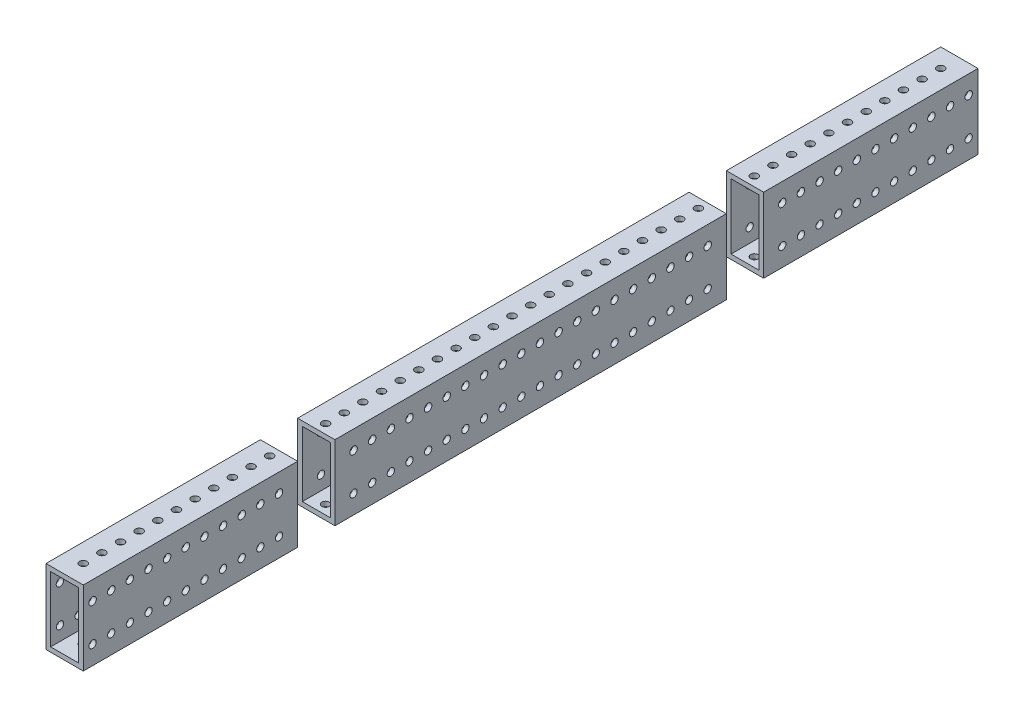
SolidWorks part; units mm, degrees
material "6061-T6 (SS)"
ref_plane "Front Plane" through (0, 0, 0) normal (0, 0, 1) x (1, 0, 0)
ref_plane "Top Plane" through (0, 0, 0) normal (0, 1, 0) x (1, 0, 0)
ref_plane "Right Plane" through (0, 0, 0) normal (1, 0, 0) x (0, 0, -1)
sketch "Sketch1" plane through (0, 0, 0) normal (0, 0, 1) x (1, 0, 0)
  line L0 (-9.525, 22.225) -> (9.525, 22.225)
  line L1 (-12.7, 25.4) -> (12.7, 25.4)
  line L2 (-12.7, 25.4) -> (-12.7, -25.4)
  line L3 (-12.7, -25.4) -> (12.7, -25.4)
  line L4 (12.7, 25.4) -> (12.7, -25.4)
  line L5 (9.525, 22.225) -> (9.525, -22.225)
  line L6 (-9.525, -22.225) -> (9.525, -22.225)
  line L7 (-9.525, 22.225) -> (-9.525, -22.225)
  line L8 (-12.7, 25.4) -> (12.7, -25.4) construction
  line L9 (12.7, 25.4) -> (-12.7, -25.4) construction
  point P5 (0, 0)
  dimension "D1" = 25.4
  dimension "D2" = 50.8
  dimension "D3" = 3.175
extrude "Boss-Extrude1" add sketch "Sketch1" along normal mid plane 609.6
sketch "Sketch2" plane through (0, 25.4, 0) normal (0, 1, 0) x (1, 0, 0)
  line L0 (12.7, -304.8) -> (-12.7, -304.8) construction
  line L1 (-12.7, -304.8) -> (-12.7, 304.8) construction
  line L4 (12.7, 304.8) -> (-12.7, 304.8) construction
  circle A0 centre (12.7, -292.1) radius 2.5527 construction
  circle A1 centre (25.4, -292.1) radius 2.5527 construction
  circle A2 centre (0, -292.1) radius 2.5527
  circle A3 centre (0, -279.4) radius 2.5527
  circle A4 centre (12.7, -279.4) radius 2.5527 construction
  circle A5 centre (25.4, -279.4) radius 2.5527 construction
  circle A6 centre (0, -266.7) radius 2.5527
  circle A7 centre (12.7, -266.7) radius 2.5527 construction
  circle A8 centre (25.4, -266.7) radius 2.5527 construction
  circle A9 centre (0, -254) radius 2.5527
  circle A10 centre (12.7, -254) radius 2.5527 construction
  circle A11 centre (25.4, -254) radius 2.5527 construction
  circle A12 centre (0, -241.3) radius 2.5527
  circle A13 centre (12.7, -241.3) radius 2.5527 construction
  circle A14 centre (25.4, -241.3) radius 2.5527 construction
  circle A15 centre (0, -228.6) radius 2.5527
  circle A16 centre (12.7, -228.6) radius 2.5527 construction
  circle A17 centre (25.4, -228.6) radius 2.5527 construction
  circle A18 centre (0, -215.9) radius 2.5527
  circle A19 centre (12.7, -215.9) radius 2.5527 construction
  circle A20 centre (25.4, -215.9) radius 2.5527 construction
  circle A21 centre (0, -203.2) radius 2.5527
  circle A22 centre (12.7, -203.2) radius 2.5527 construction
  circle A23 centre (25.4, -203.2) radius 2.5527 construction
  circle A24 centre (0, -190.5) radius 2.5527
  circle A25 centre (12.7, -190.5) radius 2.5527 construction
  circle A26 centre (25.4, -190.5) radius 2.5527 construction
  circle A27 centre (0, -177.8) radius 2.5527
  circle A28 centre (12.7, -177.8) radius 2.5527 construction
  circle A29 centre (25.4, -177.8) radius 2.5527 construction
  circle A30 centre (0, -165.1) radius 2.5527
  circle A31 centre (12.7, -165.1) radius 2.5527 construction
  circle A32 centre (25.4, -165.1) radius 2.5527 construction
  circle A33 centre (0, -152.4) radius 2.5527
  circle A34 centre (12.7, -152.4) radius 2.5527 construction
  circle A35 centre (25.4, -152.4) radius 2.5527 construction
  circle A36 centre (0, -139.7) radius 2.5527
  circle A37 centre (12.7, -139.7) radius 2.5527 construction
  circle A38 centre (25.4, -139.7) radius 2.5527 construction
  circle A39 centre (0, -127) radius 2.5527
  circle A40 centre (12.7, -127) radius 2.5527 construction
  circle A41 centre (25.4, -127) radius 2.5527 construction
  circle A42 centre (0, -114.3) radius 2.5527
  circle A43 centre (12.7, -114.3) radius 2.5527 construction
  circle A44 centre (25.4, -114.3) radius 2.5527 construction
  circle A45 centre (0, -101.6) radius 2.5527
  circle A46 centre (12.7, -101.6) radius 2.5527 construction
  circle A47 centre (25.4, -101.6) radius 2.5527 construction
  circle A48 centre (0, -88.9) radius 2.5527
  circle A49 centre (12.7, -88.9) radius 2.5527 construction
  circle A50 centre (25.4, -88.9) radius 2.5527 construction
  circle A51 centre (0, -76.2) radius 2.5527
  circle A52 centre (12.7, -76.2) radius 2.5527 construction
  circle A53 centre (25.4, -76.2) radius 2.5527 construction
  circle A54 centre (0, -63.5) radius 2.5527
  circle A55 centre (12.7, -63.5) radius 2.5527 construction
  circle A56 centre (25.4, -63.5) radius 2.5527 construction
  circle A57 centre (0, -50.8) radius 2.5527
  circle A58 centre (12.7, -50.8) radius 2.5527 construction
  circle A59 centre (25.4, -50.8) radius 2.5527 construction
  circle A60 centre (0, -38.1) radius 2.5527
  circle A61 centre (12.7, -38.1) radius 2.5527 construction
  circle A62 centre (25.4, -38.1) radius 2.5527 construction
  circle A63 centre (0, -25.4) radius 2.5527
  circle A64 centre (12.7, -25.4) radius 2.5527 construction
  circle A65 centre (25.4, -25.4) radius 2.5527 construction
  circle A66 centre (0, -12.7) radius 2.5527
  circle A67 centre (12.7, -12.7) radius 2.5527 construction
  circle A68 centre (25.4, -12.7) radius 2.5527 construction
  circle A69 centre (0, 0) radius 2.5527
  circle A70 centre (12.7, 0) radius 2.5527 construction
  circle A71 centre (25.4, 0) radius 2.5527 construction
  circle A72 centre (0, 12.7) radius 2.5527
  circle A73 centre (12.7, 12.7) radius 2.5527 construction
  circle A74 centre (25.4, 12.7) radius 2.5527 construction
  circle A75 centre (0, 25.4) radius 2.5527
  circle A76 centre (12.7, 25.4) radius 2.5527 construction
  circle A77 centre (25.4, 25.4) radius 2.5527 construction
  circle A78 centre (0, 38.1) radius 2.5527
  circle A79 centre (12.7, 38.1) radius 2.5527 construction
  circle A80 centre (25.4, 38.1) radius 2.5527 construction
  circle A81 centre (0, 50.8) radius 2.5527
  circle A82 centre (12.7, 50.8) radius 2.5527 construction
  circle A83 centre (25.4, 50.8) radius 2.5527 construction
  circle A84 centre (0, 63.5) radius 2.5527
  circle A85 centre (12.7, 63.5) radius 2.5527 construction
  circle A86 centre (25.4, 63.5) radius 2.5527 construction
  circle A87 centre (0, 76.2) radius 2.5527
  circle A88 centre (12.7, 76.2) radius 2.5527 construction
  circle A89 centre (25.4, 76.2) radius 2.5527 construction
  circle A90 centre (0, 88.9) radius 2.5527
  circle A91 centre (12.7, 88.9) radius 2.5527 construction
  circle A92 centre (25.4, 88.9) radius 2.5527 construction
  circle A93 centre (0, 101.6) radius 2.5527
  circle A94 centre (12.7, 101.6) radius 2.5527 construction
  circle A95 centre (25.4, 101.6) radius 2.5527 construction
  circle A96 centre (0, 114.3) radius 2.5527
  circle A97 centre (12.7, 114.3) radius 2.5527 construction
  circle A98 centre (25.4, 114.3) radius 2.5527 construction
  circle A99 centre (0, 127) radius 2.5527
  circle A100 centre (12.7, 127) radius 2.5527 construction
  circle A101 centre (25.4, 127) radius 2.5527 construction
  circle A108 centre (0, 152.4) radius 2.5527 [skipped]
  circle A109 centre (12.7, 152.4) radius 2.5527 [skipped]
  circle A110 centre (25.4, 152.4) radius 2.5527 [skipped]
  circle A111 centre (0, 139.7) radius 2.5527 [skipped]
  circle A112 centre (12.7, 139.7) radius 2.5527 [skipped]
  circle A113 centre (25.4, 139.7) radius 2.5527 [skipped]
  circle A114 centre (25.4, 139.7) radius 2.5527 construction
  circle A115 centre (12.7, 139.7) radius 2.5527 construction
  circle A116 centre (0, 139.7) radius 2.5527
  circle A117 centre (25.4, 152.4) radius 2.5527 construction
  circle A118 centre (12.7, 152.4) radius 2.5527 construction
  circle A119 centre (0, 152.4) radius 2.5527
  circle A120 centre (25.4, 165.1) radius 2.5527 construction
  circle A121 centre (12.7, 165.1) radius 2.5527 construction
  circle A122 centre (0, 165.1) radius 2.5527
  circle A123 centre (25.4, 177.8) radius 2.5527 construction
  circle A124 centre (12.7, 177.8) radius 2.5527 construction
  circle A125 centre (0, 177.8) radius 2.5527
  circle A126 centre (25.4, 190.5) radius 2.5527 construction
  circle A127 centre (12.7, 190.5) radius 2.5527 construction
  circle A128 centre (0, 190.5) radius 2.5527
  circle A129 centre (25.4, 203.2) radius 2.5527 construction
  circle A130 centre (12.7, 203.2) radius 2.5527 construction
  circle A131 centre (0, 203.2) radius 2.5527
  circle A132 centre (25.4, 215.9) radius 2.5527 construction
  circle A133 centre (12.7, 215.9) radius 2.5527 construction
  circle A134 centre (0, 215.9) radius 2.5527
  circle A135 centre (25.4, 228.6) radius 2.5527 construction
  circle A136 centre (12.7, 228.6) radius 2.5527 construction
  circle A137 centre (0, 228.6) radius 2.5527
  circle A138 centre (25.4, 241.3) radius 2.5527 construction
  circle A139 centre (12.7, 241.3) radius 2.5527 construction
  circle A140 centre (0, 241.3) radius 2.5527
  circle A141 centre (25.4, 254) radius 2.5527 construction
  circle A142 centre (12.7, 254) radius 2.5527 construction
  circle A143 centre (0, 254) radius 2.5527
  circle A144 centre (25.4, 266.7) radius 2.5527 construction
  circle A145 centre (12.7, 266.7) radius 2.5527 construction
  circle A146 centre (0, 266.7) radius 2.5527
  circle A147 centre (25.4, 279.4) radius 2.5527 construction
  circle A148 centre (12.7, 279.4) radius 2.5527 construction
  circle A149 centre (0, 279.4) radius 2.5527
  circle A150 centre (25.4, 292.1) radius 2.5527 construction
  circle A151 centre (12.7, 292.1) radius 2.5527 construction
  circle A152 centre (0, 292.1) radius 2.5527
  dimension "D2" = 5.1054
  dimension "D4" = 12.7
  dimension "D1" = 12.7
  dimension "D3" = 25.4
  dimension "D6" = 12.7
  dimension "D7" = 177.8
  dimension "D5" = 36
  dimension "D8" = 14
extrude "Cut-Extrude1" cut sketch "Sketch2" against normal through all
sketch "Sketch4" plane through (12.7, 0, 0) normal (1, 0, 0) x (0, 0, -1)
  line L0 (-304.8, 25.4) -> (304.8, 25.4) construction
  line L1 (-304.8, -25.4) -> (-304.8, 25.4) construction
  line L2 (-304.8, -25.4) -> (304.8, -25.4) construction
  line L3 (-304.8, 25.4) -> (-304.8, -25.4) construction
  circle A2 centre (-298.45, -12.7) radius 2.4892
  circle A3 centre (-285.75, -12.7) radius 2.4892
  circle A16 centre (-273.05, -12.7) radius 2.4892
  circle A17 centre (-260.35, -12.7) radius 2.4892
  circle A18 centre (-247.65, -12.7) radius 2.4892
  circle A19 centre (133.35, -12.7) radius 2.4892 construction
  circle A20 centre (146.05, -12.7) radius 2.4892
  circle A21 centre (158.75, -12.7) radius 2.4892 construction
  circle A22 centre (171.45, -12.7) radius 2.4892
  circle A23 centre (184.15, -12.7) radius 2.4892
  circle A24 centre (196.85, -12.7) radius 2.4892
  circle A25 centre (209.55, -12.7) radius 2.4892
  circle A26 centre (222.25, -12.7) radius 2.4892
  circle A27 centre (234.95, -12.7) radius 2.4892
  circle A28 centre (247.65, -12.7) radius 2.4892
  circle A29 centre (260.35, -12.7) radius 2.4892
  circle A30 centre (273.05, -12.7) radius 2.4892
  circle A31 centre (285.75, -12.7) radius 2.4892
  circle A32 centre (298.45, -12.7) radius 2.4892
  circle A33 centre (-298.45, 12.7) radius 2.5527
  circle A34 centre (-285.75, 12.7) radius 2.5527
  circle A35 centre (-234.95, -12.7) radius 2.4892
  circle A36 centre (-222.25, -12.7) radius 2.4892
  circle A37 centre (-209.55, -12.7) radius 2.4892
  circle A38 centre (-196.85, -12.7) radius 2.4892
  circle A39 centre (-184.15, -12.7) radius 2.4892
  circle A40 centre (-171.45, -12.7) radius 2.4892
  circle A41 centre (-158.75, -12.7) radius 2.4892 construction
  circle A42 centre (-146.05, -12.7) radius 2.4892
  circle A43 centre (-133.35, -12.7) radius 2.4892 construction
  circle A44 centre (-120.65, -12.7) radius 2.4892
  circle A45 centre (-107.95, -12.7) radius 2.4892
  circle A46 centre (-95.25, -12.7) radius 2.4892
  circle A47 centre (-82.55, -12.7) radius 2.4892
  circle A48 centre (-69.85, -12.7) radius 2.4892
  circle A49 centre (-57.15, -12.7) radius 2.4892
  circle A50 centre (-44.45, -12.7) radius 2.4892
  circle A51 centre (-31.75, -12.7) radius 2.4892
  circle A52 centre (-19.05, -12.7) radius 2.4892
  circle A53 centre (-6.35, -12.7) radius 2.4892
  circle A54 centre (6.35, -12.7) radius 2.4892
  circle A55 centre (19.05, -12.7) radius 2.4892
  circle A56 centre (31.75, -12.7) radius 2.4892
  circle A57 centre (44.45, -12.7) radius 2.4892
  circle A58 centre (57.15, -12.7) radius 2.4892
  circle A59 centre (69.85, -12.7) radius 2.4892
  circle A60 centre (82.55, -12.7) radius 2.4892
  circle A61 centre (95.25, -12.7) radius 2.4892
  circle A62 centre (107.95, -12.7) radius 2.4892
  circle A63 centre (120.65, -12.7) radius 2.4892
  circle A64 centre (-273.05, 12.7) radius 2.5527
  circle A65 centre (-260.35, 12.7) radius 2.5527
  circle A66 centre (-247.65, 12.7) radius 2.5527
  circle A67 centre (-234.95, 12.7) radius 2.5527
  circle A68 centre (-222.25, 12.7) radius 2.5527
  circle A69 centre (-209.55, 12.7) radius 2.5527
  circle A70 centre (-196.85, 12.7) radius 2.5527
  circle A71 centre (-184.15, 12.7) radius 2.5527
  circle A72 centre (-171.45, 12.7) radius 2.5527
  circle A73 centre (-158.75, 12.7) radius 2.5527 construction
  circle A74 centre (-146.05, 12.7) radius 2.5527
  circle A75 centre (-133.35, 12.7) radius 2.5527 construction
  circle A76 centre (-120.65, 12.7) radius 2.5527
  circle A77 centre (-107.95, 12.7) radius 2.5527
  circle A78 centre (-95.25, 12.7) radius 2.5527
  circle A79 centre (-82.55, 12.7) radius 2.5527
  circle A80 centre (-69.85, 12.7) radius 2.5527
  circle A81 centre (-57.15, 12.7) radius 2.5527
  circle A82 centre (-44.45, 12.7) radius 2.5527
  circle A83 centre (-31.75, 12.7) radius 2.5527
  circle A84 centre (-19.05, 12.7) radius 2.5527
  circle A85 centre (-6.35, 12.7) radius 2.5527
  circle A86 centre (6.35, 12.7) radius 2.5527
  circle A87 centre (19.05, 12.7) radius 2.5527
  circle A88 centre (31.75, 12.7) radius 2.5527
  circle A89 centre (44.45, 12.7) radius 2.5527
  circle A90 centre (57.15, 12.7) radius 2.5527
  circle A91 centre (69.85, 12.7) radius 2.5527
  circle A92 centre (82.55, 12.7) radius 2.5527
  circle A93 centre (95.25, 12.7) radius 2.5527
  circle A94 centre (107.95, 12.7) radius 2.5527
  circle A95 centre (120.65, 12.7) radius 2.5527
  circle A96 centre (133.35, 12.7) radius 2.5527 construction
  circle A97 centre (146.05, 12.7) radius 2.5527
  circle A98 centre (158.75, 12.7) radius 2.5527 construction
  circle A99 centre (171.45, 12.7) radius 2.5527
  circle A100 centre (184.15, 12.7) radius 2.5527
  circle A101 centre (196.85, 12.7) radius 2.5527
  circle A102 centre (209.55, 12.7) radius 2.5527
  circle A103 centre (222.25, 12.7) radius 2.5527
  circle A104 centre (234.95, 12.7) radius 2.5527
  circle A105 centre (247.65, 12.7) radius 2.5527
  circle A106 centre (260.35, 12.7) radius 2.5527
  circle A107 centre (273.05, 12.7) radius 2.5527
  circle A108 centre (285.75, 12.7) radius 2.5527
  circle A109 centre (298.45, 12.7) radius 2.5527
  dimension "D2" = 4.9784
  dimension "D1" = 6.35
  dimension "D8" = 5.1054
  dimension "D9" = 12.7
  dimension "D10" = 6.35
  dimension "D11" = 48
  dimension "D12" = 12.7
  dimension "D13" = 12.7
  dimension "D14" = 12.7
  dimension "D3" = 12.7
  dimension "D4" = 12.7
  dimension "D5" = 34
  dimension "D6" = 10
  dimension "D7" = 6
extrude "Cut-Extrude3" cut sketch "Sketch4" against normal through all
sketch "Sketch6" plane through (-12.7, 0, 0) normal (-1, 0, 0) x (0, 0, 1)
  line L0 (-304.8, 25.4) -> (-304.8, -25.4) construction
  line L1 (304.8, 25.4) -> (-304.8, 25.4) construction
  line L2 (304.8, -25.4) -> (-304.8, -25.4) construction
  line L3 (-158.75, 25.4) -> (-133.35, 25.4)
  line L4 (-158.75, 25.4) -> (-158.75, -25.4)
  line L5 (-158.75, -25.4) -> (-133.35, -25.4)
  line L6 (-133.35, 25.4) -> (-133.35, -25.4)
  line L7 (158.75, -25.4) -> (133.35, -25.4)
  line L8 (158.75, -25.4) -> (158.75, 25.4)
  line L9 (158.75, 25.4) -> (133.35, 25.4)
  line L10 (133.35, -25.4) -> (133.35, 25.4)
  line L12 (304.8, 25.4) -> (304.8, -25.4) construction
  dimension "D1" = 25.4
  dimension "D2" = 146.05
  dimension "D3" = 25.4
  dimension "D4" = 146.05
extrude "Cut-Extrude4" cut sketch "Sketch6" against normal through all
